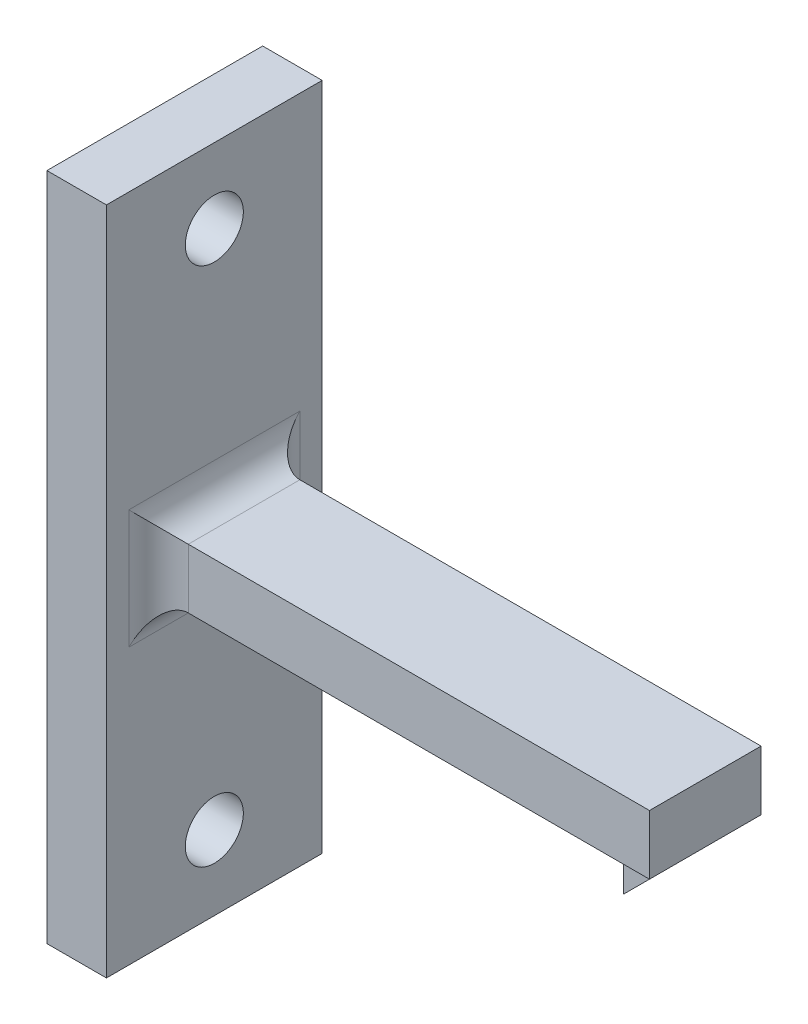
SolidWorks part; units mm, degrees
ref_plane "Front Plane" through (0, 0, 0) normal (0, 0, 1) x (1, 0, 0)
ref_plane "Top Plane" through (0, 0, 0) normal (0, 1, 0) x (1, 0, 0)
ref_plane "Right Plane" through (0, 0, 0) normal (1, 0, 0) x (0, 0, -1)
ref_plane "Plane1" through (0, 0, -2.5) normal (0, 0, 1) x (1, 0, 0)
sketch "Sketch2" plane through (0, 0, -2.5) normal (0, 0, 1) x (1, 0, 0)
  line L0 (230.0241, 2) -> (225.0241, 2)
  line L1 (225.0241, 2) -> (225.0241, -2)
  line L2 (225.0241, -2) -> (230.0241, -2)
  circle A0 centre (230.0241, 0) radius 1 construction
  circle A1 centre (230.0241, 0) radius 1
  circle A2 centre (230.0241, 0) radius 2
  dimension "D1" = 1
  dimension "D2" = 5
extrude "Boss-Extrude1" add sketch "Sketch2" along normal blind 1 and the other way blind 1 contours A2 L0 L1 L2 | A2 A1 region at (226.7677, 0, -2.5) region at (231.3983, 1.3742, -2.5)
sketch "Sketch3" plane through (0, 2, 0) normal (0, 1, 0) x (1, 0, 0)
  line L0 (225.0241, 1.5) -> (222.0241, -5.5)
  line L1 (222.0241, -5.5) -> (216.0955, -5.5)
  line L2 (216.0955, 10.5) -> (216.0955, 8.5)
  line L3 (216.0955, 10.5) -> (222.0241, 10.5)
  line L4 (225.0241, 3.5) -> (225.0241, 1.5)
  line L5 (225.0241, 1.5) -> (230.0241, 1.5)
  line L6 (230.0241, 1.5) -> (230.0241, 3.5)
  line L7 (230.0241, 3.5) -> (225.0241, 3.5)
  line L8 (225.0241, 3.5) -> (225.0241, 1.5)
  line L9 (225.0241, 1.5) -> (230.0241, 1.5)
  line L10 (230.0241, 1.5) -> (230.0241, 3.5)
  line L11 (230.0241, 3.5) -> (225.0241, 3.5)
  line L12 (222.0241, 10.5) -> (225.0241, 3.5)
  line L13 (216.0955, 8.5) -> (221.0955, 8.5)
  line L14 (221.0955, 8.5) -> (223.0241, 4)
  line L15 (223.0241, 4) -> (223.0241, 1)
  line L16 (230.0241, 2.5) -> (208.0852, 2.5) construction
  line L17 (139.7, 2.5) -> (266.7, 2.5) construction
  line L18 (216.0955, -5.5) -> (216.0955, -3.5)
  line L19 (221.0955, -3.5) -> (223.0241, 1)
  line L20 (216.0955, -3.5) -> (221.0955, -3.5)
  line M15 (225.0241, 3.5) -> (225.0241, 1.5)
  dimension "D2" = 2
  dimension "D3" = 5
  dimension "D4" = 2
  dimension "D5" = 7
  dimension "D6" = 3
  dimension "D7" = 3
  dimension "D1" = 0
extrude "Boss-Extrude2" add sketch "Sketch3" against normal up to surface (4 mm away) contours L16 L12 L3 L2 L13 L14 L15 M15 | L8 L16 L15 L19 L20 L18 L1 L0 region at (223.4139, 2, 1.9528) region at (224.0241, 2, -2.6199) up to face at (227.5241, -2, -2.5)
sketch "Sketch4" plane through (0, 0, -10.5) normal (0, 0, -1) x (-1, 0, 0)
  line L0 (-216.0955, 0) -> (-218.0955, 0)
  line L1 (-139.7, 0) -> (-266.7, 0) construction
  line L4 (-222.0241, -2) -> (-216.0955, -2)
  line L5 (-216.0955, -2) -> (-216.0955, 2)
  line L6 (-216.0955, 2) -> (-222.0241, 2)
  line L7 (-222.0241, 2) -> (-222.0241, -2)
  line L8 (-222.0241, -2) -> (-216.0955, -2)
  line L9 (-216.0955, -2) -> (-216.0955, 2)
  line L10 (-216.0955, 2) -> (-222.0241, 2)
  line L11 (-222.0241, 2) -> (-222.0241, -2)
  circle A0 centre (-218.0955, 0) radius 1.07
  dimension "D2" = 2.14
  dimension "D3" = 2
  dimension "D1" = 0
extrude "Cut-Extrude1" cut sketch "Sketch4" against normal through all contours A0 region at (219.1352, 0, -10.5)
sketch "Sketch6" plane through (0, 0, -1.5) normal (0, 0, 1) x (1, 0, 0)
  line L0 (230.0241, 2) -> (258.0241, 2)
  line L1 (258.0241, 2) -> (258.0241, -2)
  line L2 (258.0241, -2) -> (230.0241, -2)
  line L3 (230.0241, 2) -> (228.1025, 2)
  line L4 (230.0241, 2) -> (225.0241, 2) construction
  line L5 (228.1025, 2) -> (228.1025, -2)
  line L6 (225.0241, -2) -> (230.0241, -2) construction
  line L7 (228.1025, -2) -> (230.0241, -2)
  arc A0 (230.0241, -2) -> (230.0241, 2) centre (230.0241, 0) ccw construction
  dimension "D1" = 28
extrude "Boss-Extrude3" add sketch "Sketch6" against normal blind 2
sketch "Sketch8" plane through (0, 0, -3.5) normal (0, 0, -1) x (-1, 0, 0)
  line L0 (-258.0241, -2) -> (-254.0241, -6)
  line L1 (-258.0241, 2) -> (-254.0241, 2)
  line L2 (-258.0241, 2) -> (-258.0241, -6)
  line L3 (-258.0241, -6) -> (-254.0241, -6)
  line L4 (-254.0241, 2) -> (-254.0241, -6)
  dimension "D1" = 4
  dimension "D2" = 8
extrude "Boss-Extrude4" add sketch "Sketch8" against normal blind 2 contours L2 L1 L4 L3
sketch "Sketch9" plane through (0, 0, -3.5) normal (0, 0, -1) x (-1, 0, 0)
  line L0 (-254.0241, -6) -> (-258.0241, -6)
  line L1 (-258.0241, -6) -> (-258.0241, -2)
  line L2 (-258.0241, -6) -> (-258.0241, 2) construction
  line L3 (-258.0241, -2) -> (-254.0241, -6)
extrude "Cut-Extrude2" cut sketch "Sketch9" against normal blind 2
sketch "Sketch10" plane through (0, 0, -3.5) normal (0, 0, -1) x (-1, 0, 0)
  line L0 (-258.0241, -2) -> (-258.0241, 2) construction
  line L1 (-258.0241, -2) -> (-223.5241, -2)
  line L2 (-258.0241, -2) -> (-258.0241, 2)
  line L3 (-258.0241, 2) -> (-223.5241, 2)
  line L4 (-223.5241, -2) -> (-223.5241, 2)
  line L5 (-222.0241, 2) -> (-225.0241, 2) construction
extrude "Boss-Extrude5" add sketch "Sketch10" along normal blind 2.75
sketch "Sketch11" plane through (0, 0, -1.5) normal (0, 0, 1) x (1, 0, 0)
  line L0 (225.0241, -2) -> (222.0241, -2) construction
  line L1 (258.0241, 2) -> (223.5241, 2)
  line L2 (258.0241, 2) -> (258.0241, -2)
  line L3 (258.0241, -2) -> (223.5241, -2)
  line L4 (223.5241, 2) -> (223.5241, -2)
extrude "Boss-Extrude6" add sketch "Sketch11" along normal blind 2.75
sketch "Sketch12" plane through (0, 0, -3.5) normal (0, 0, -1) x (-1, 0, 0)
  line L0 (-258.0241, -2) -> (-254.0241, -6)
  line L1 (-254.0241, -6) -> (-254.0241, -2)
  line L2 (-254.0241, -2) -> (-258.0241, -2)
extrude "Boss-Extrude7" add sketch "Sketch12" along normal blind 0.5
sketch "Sketch13" plane through (0, 0, -1.5) normal (0, 0, 1) x (1, 0, 0)
  line L0 (254.0241, -2) -> (254.0241, -6)
  line L1 (254.0241, -6) -> (258.0241, -2)
  line L2 (258.0241, -2) -> (254.0241, -2)
extrude "Boss-Extrude8" add sketch "Sketch13" along normal blind 0.5
sketch "Sketch14" plane through (0, 0, -6.25) normal (0, 0, -1) x (-1, 0, 0)
  line L0 (-223.8455, 2) -> (-258.0241, 2) construction
  line L1 (-224.804, 2) -> (-223.0241, 2)
  line L2 (-224.804, 2) -> (-224.804, -2)
  line L3 (-224.804, -2) -> (-223.0241, -2)
  line L4 (-223.0241, 2) -> (-223.0241, -2)
extrude "Boss-Extrude9" add sketch "Sketch14" against normal up to surface (7.5 mm away) up to face at (240.9348, 0, 1.25)
sketch "Sketch15" plane through (223.0241, 0, 0) normal (-1, 0, 0) x (0, 0, 1)
  line L0 (-4, 2) -> (-1, -2) construction
  line L2 (-22.5, -13.6568) -> (17.5, -13.6568)
  line L3 (-22.5, -13.6568) -> (-22.5, 13.6568)
  line L4 (-22.5, 13.6568) -> (17.5, 13.6568)
  line L5 (17.5, -13.6568) -> (17.5, 13.6568)
  line L6 (-22.5, -13.6568) -> (17.5, 13.6568) construction
  line L7 (-22.5, 13.6568) -> (17.5, -13.6568) construction
  point P4 (-2.5, 0)
  dimension "D1" = 40
extrude "Cut-Extrude3" cut sketch "Sketch15" along normal blind 10 and the other way blind 2
sketch "Sketch16" plane through (225.0241, 0, 0) normal (-1, 0, 0) x (0, 0, 1)
  line L0 (-6.25, 2) -> (1.25, -2) construction
  line L1 (-6.25, -2) -> (1.25, 2) construction
  line L3 (-9.75, -22.5) -> (4.75, -22.5)
  line L4 (-9.75, -22.5) -> (-9.75, 22.5)
  line L5 (-9.75, 22.5) -> (4.75, 22.5)
  line L6 (4.75, -22.5) -> (4.75, 22.5)
  line L7 (-9.75, -22.5) -> (4.75, 22.5) construction
  line L8 (-9.75, 22.5) -> (4.75, -22.5) construction
  point P8 (-2.5, 0)
  dimension "D1" = 14.5
  dimension "D2" = 45
extrude "Boss-Extrude10" add sketch "Sketch16" along normal blind 4
sketch "Sketch18" plane through (221.0241, 0, 0) normal (-1, 0, 0) x (0, 0, 1)
  line L0 (-9.75, 22.5) -> (4.75, -22.5) construction
  line L1 (-9.75, -22.5) -> (4.75, 22.5) construction
  line L2 (4.75, 22.5) -> (-9.75, 22.5) construction
  line L3 (-9.75, -22.5) -> (4.75, -22.5) construction
  circle A0 centre (-2.5, 17.5) radius 1.95
  circle A1 centre (-2.5, -17.5) radius 1.95
  dimension "D3" = 3.9
  dimension "D4" = 3.9
  dimension "D1" = 5
  dimension "D2" = 5
extrude "Cut-Extrude4" cut sketch "Sketch18" against normal blind 4
fillet "Fillet1" radius 2 4 edges at (225.0241, -2, -2.5) (225.0241, 0, 1.25) (225.0241, 2, -2.5) (225.0241, 0, -6.25)
